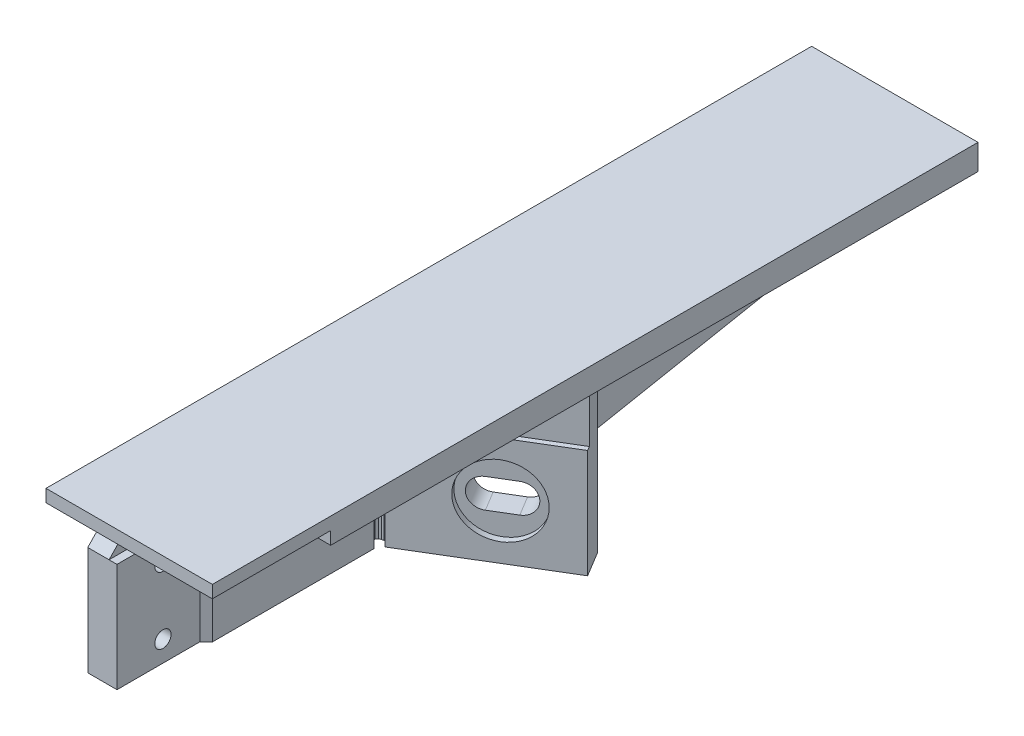
SolidWorks part; units mm, degrees
ref_plane "Front Plane" through (0, 0, 0) normal (0, 0, 1) x (1, 0, 0)
ref_plane "Top Plane" through (0, 0, 0) normal (0, 1, 0) x (1, 0, 0)
ref_plane "Right Plane" through (0, 0, 0) normal (1, 0, 0) x (0, 0, -1)
ref_plane "PY -20.700" through (0, -20.7, 0) normal (0, 1, 0) x (1, 0, 0)
sketch "leg and pad sketch" plane through (0, -20.7, 0) normal (0, 1, 0) x (1, 0, 0)
  line L0 (0.5513, 30.3327) -> (0.3673, 30.8194)
  line L1 (0.3673, 30.8194) -> (0.028, 31.2139)
  line L2 (0.028, 31.2139) -> (-0.4256, 31.4688)
  line L3 (-0.4256, 31.4688) -> (-0.939, 31.5534)
  line L4 (-0.939, 31.5534) -> (-1.4504, 31.4576)
  line L5 (-1.4504, 31.4576) -> (-1.8983, 31.1928)
  line L6 (-1.8983, 31.1928) -> (-2.2288, 30.7909)
  line L7 (-2.2288, 30.7909) -> (-2.4021, 30.3003)
  line L8 (-2.4021, 30.3003) -> (-2.3973, 29.78)
  line L9 (-2.3973, 29.78) -> (-2.2152, 29.2926)
  line L10 (-2.2152, 29.2926) -> (-1.8775, 28.8968)
  line L11 (-1.8775, 28.8968) -> (-1.4248, 28.6402)
  line L12 (-1.4248, 28.6402) -> (-0.9118, 28.5536)
  line L13 (-0.9118, 28.5536) -> (-0.4, 28.6475)
  line L14 (-0.4, 28.6475) -> (-0.4, -9.98)
  line L15 (-0.4, -9.98) -> (-1.92, -11.5)
  line L16 (-1.92, -11.5) -> (-1.92, -31.37)
  line L17 (-1.92, -31.37) -> (-8.92, -31.37)
  line L18 (-8.92, -31.37) -> (-8.92, 32.7926)
  line L19 (-8.92, 32.7926) -> (27.2048, 54.5947)
  line L20 (27.2048, 54.5947) -> (30.8218, 48.6015)
  line L21 (30.8218, 48.6015) -> (0.5513, 30.3327)
extrude "leg and pad" add sketch "leg and pad sketch" along normal mid plane 26
ref_plane "PX -1.350" through (-1.35, 0, 0) normal (1, 0, 0) x (0, 0, -1)
sketch "screw head relief sketch" plane through (-1.35, 0, 0) normal (1, 0, 0) x (0, 0, -1)
  line L0 (23.4, -12.7) -> (23.4, -6.7)
  line L1 (23.4, -6.7) -> (9.4, -6.7)
  line L2 (9.4, -6.7) -> (9.4, -12.7)
  line L3 (9.4, -12.7) -> (23.4, -12.7)
extrude "screw head relief" cut sketch "screw head relief sketch" against normal mid plane 4.7
sketch "insert flange relief sketch" plane through (0, -20.7, 0) normal (0, 1, 0) x (1, 0, 0)
  line L0 (18.3249, 39.8914) -> (17.0331, 42.0318)
  line L1 (17.0331, 42.0318) -> (9.7557, 37.6398)
  line L2 (9.7557, 37.6398) -> (11.0475, 35.4994)
  line L3 (11.0475, 35.4994) -> (18.3249, 39.8914)
revolve "insert flange relief" cut sketch "insert flange relief sketch" angle 360 about L0
sketch "M6 slot end 1 sketch" plane through (0, -20.7, 0) normal (0, 1, 0) x (1, 0, 0)
  line L0 (20.8933, 41.4415) -> (16.243, 49.147)
  line L1 (16.243, 49.147) -> (13.2464, 47.3385)
  line L2 (13.2464, 47.3385) -> (17.8968, 39.633)
  line L3 (17.8968, 39.633) -> (20.8933, 41.4415)
revolve "M6 slot end 1" cut sketch "M6 slot end 1 sketch" angle 360 about L0
sketch "M6 slot end 2 sketch" plane through (0, -20.7, 0) normal (0, 1, 0) x (1, 0, 0)
  line L0 (15.7564, 38.3413) -> (11.106, 46.0467)
  line L1 (11.106, 46.0467) -> (8.1094, 44.2382)
  line L2 (8.1094, 44.2382) -> (12.7598, 36.5328)
  line L3 (12.7598, 36.5328) -> (15.7564, 38.3413)
revolve "M6 slot end 2" cut sketch "M6 slot end 2 sketch" angle 360 about L0
sketch "M6 slot middle sketch" plane through (0, -20.7, 0) normal (0, 1, 0) x (1, 0, 0)
  line L0 (15.7564, 38.3413) -> (20.8933, 41.4415)
  line L1 (20.8933, 41.4415) -> (16.243, 49.147)
  line L2 (16.243, 49.147) -> (11.106, 46.0467)
  line L3 (11.106, 46.0467) -> (15.7564, 38.3413)
extrude "M6 slot middle" cut sketch "M6 slot middle sketch" against normal mid plane 7
ref_plane "PX -5.420" through (-5.42, 0, 0) normal (1, 0, 0) x (0, 0, -1)
sketch "screw holes sketch" plane through (-5.42, 0, 0) normal (1, 0, 0) x (0, 0, -1)
  circle A0 centre (-20.375, -28.7) radius 1.95
  circle A1 centre (-20.375, -12.7) radius 1.95
extrude "screw holes" cut sketch "screw holes sketch" against normal mid plane 9
ref_plane "PY -2.100" through (0, -2.1, 0) normal (0, 1, 0) x (1, 0, 0)
sketch "foot leg sketch" plane through (0, -2.1, 0) normal (0, 1, 0) x (1, 0, 0)
  line L0 (-2.3, 30.0135) -> (-2.3, -9.98)
  line L1 (-2.3, -9.98) -> (-8.92, -9.98)
  line L2 (-8.92, -9.98) -> (-8.92, 32.7926)
  line L3 (-8.92, 32.7926) -> (27.2048, 54.5947)
  line L4 (27.2048, 54.5947) -> (30.2017, 49.6289)
  line L5 (30.2017, 49.6289) -> (-2.3, 30.0135)
extrude "foot leg" add sketch "foot leg sketch" along normal mid plane 12.2
ref_plane "PY 6.535" through (0, 6.535, 0) normal (0, 1, 0) x (1, 0, 0)
sketch "sole under the housing sketch" plane through (0, 6.535, 0) normal (0, 1, 0) x (1, 0, 0)
  line L0 (30.9218, 142) -> (-8.92, 142)
  line L1 (-8.92, 142) -> (-8.92, -13.03)
  line L2 (-8.92, -13.03) -> (30.9218, -13.03)
  line L3 (30.9218, -13.03) -> (30.9218, 142)
extrude "sole under the housing" add sketch "sole under the housing sketch" along normal mid plane 6.07
ref_plane "PY 8.070" through (0, 8.07, 0) normal (0, 1, 0) x (1, 0, 0)
sketch "sole under the block sketch" plane through (0, 8.07, 0) normal (0, 1, 0) x (1, 0, 0)
  line L0 (30.9218, -12.53) -> (-8.92, -12.53)
  line L1 (-8.92, -12.53) -> (-8.92, -41.37)
  line L2 (-8.92, -41.37) -> (30.9218, -41.37)
  line L3 (30.9218, -41.37) -> (30.9218, -12.53)
extrude "sole under the block" add sketch "sole under the block sketch" along normal mid plane 3
ref_plane "PX -6.370" through (-6.37, 0, 0) normal (1, 0, 0) x (0, 0, -1)
sketch "seat gusset sketch" plane through (-6.37, 0, 0) normal (1, 0, 0) x (0, 0, -1)
  line L0 (-9.48, -8.2) -> (-31.37, -8.2)
  line L1 (-31.37, -8.2) -> (-31.37, -7.7)
  line L2 (-31.37, -7.7) -> (-17.1, 7.07)
  line L3 (-17.1, 7.07) -> (-9.48, 7.07)
  line L4 (-9.48, 7.07) -> (-9.48, -8.2)
extrude "seat gusset" add sketch "seat gusset sketch" along normal mid plane 5.1
ref_plane "PX 19.922" through (19.9218, 0, 0) normal (1, 0, 0) x (0, 0, -1)
sketch "tail rib sketch" plane through (19.9218, 0, 0) normal (1, 0, 0) x (0, 0, -1)
  line L0 (53.1, 4) -> (53.1, -12.5)
  line L1 (53.1, -12.5) -> (57.1, -12.5)
  line L2 (57.1, -12.5) -> (140, 3.5)
  line L3 (140, 3.5) -> (140, 4)
  line L4 (140, 4) -> (53.1, 4)
extrude "tail rib" add sketch "tail rib sketch" along normal mid plane 6
sketch "screw head relief to the end sketch" plane through (-1.35, 0, 0) normal (1, 0, 0) x (0, 0, -1)
  line L0 (23.4, -12.7) -> (23.4, 3.3)
  line L1 (23.4, 3.3) -> (9.4, 3.3)
  line L2 (9.4, 3.3) -> (9.4, -12.7)
  line L3 (9.4, -12.7) -> (23.4, -12.7)
extrude "screw head relief to the end" cut sketch "screw head relief to the end sketch" against normal mid plane 4.7
equation "\"diffL\" = 608.8mm"
equation "\"diffW\" = 329.4mm"
equation "\"diffT\" = 2.9mm"
equation "\"chanSlotW\" = 12.9mm"
equation "\"chanSlotDepth\" = 11.13mm"
equation "\"chanFloor\" = 1.57mm"
equation "\"chanLeg\" = 12.7mm"
equation "\"lightL\" = 604.8mm"
equation "\"lightW\" = 330.2mm"
equation "\"lightH\" = 92mm"
equation "\"lightSideFlat\" = 30mm"
equation "\"lightSlopeLen\" = 38.9mm"
equation "\"lightWingDepth\" = 50.1mm"
equation "\"lightWingFlat\" = 90.2mm"
equation "\"lightChanW\" = 99.6mm"
equation "\"lightChanStand\" = 44.1mm"
equation "\"insFlangeD\" = 12.3mm"
equation "\"insFromEnd\" = 20.7mm"
equation "\"insUpSlope\" = 20.8mm"
equation "\"gaugeH\" = 10mm"
equation "\"gaugeStepLen\" = 14mm"
equation "\"gaugeStepW0\" = 13.1mm"
equation "\"gaugeStepDW\" = 0.2mm"
equation "\"gaugeSteps\" = 5mm"
equation "\"gaugeHandleLen\" = 30mm"
equation "\"gaugeHandleW\" = 24mm"
equation "\"gaugeSlot0\" = 3mm"
equation "\"gaugeSlotD\" = 0.1mm"
equation "\"gaugeSlotDepth\" = 8mm"
equation "\"gap\" = 25.4mm"
equation "\"edgeL\" = 1mm"
equation "\"edgeW\" = 0.75mm"
equation "\"proud\" = 1.5mm"
equation "\"seatClr\" = 0.15mm"
equation "\"tongueClrZ\" = 0.1mm"
equation "\"tongueClrX\" = 0.25mm"
equation "\"tongueLen\" = 30mm"
equation "\"armSide\" = 45mm"
equation "\"armEnd\" = 20mm"
equation "\"cornerCham\" = 3mm"
equation "\"brkW\" = 26mm"
equation "\"brkT\" = 7mm"
equation "\"brkSeatClr\" = 0.3mm"
equation "\"brkScrewSpan\" = 16mm"
equation "\"pilotD\" = 2.7mm"
equation "\"pilotDepth\" = 10mm"
equation "\"screwClrD\" = 3.9mm"
equation "\"jogBelow\" = 4mm"
equation "\"padT\" = 7mm"
equation "\"padLen\" = 36mm"
equation "\"m6Clr\" = 7mm"
equation "\"m6Slot\" = 6mm"
equation "\"flangeRelD\" = 17mm"
equation "\"flangeRelDepth\" = 1.5mm"
equation "\"relLen\" = 5mm"
equation "\"relDepth\" = 3.3mm"
equation "\"knockN\" = 100mm"
equation "\"petgcfE\" = 3000mm"
equation "\"mockExtent\" = 110mm"
equation "\"relZnear\" = 9.4mm"
equation "\"relZfar\" = 23.4mm"
equation "\"headD\" = 8mm"
equation "\"headH\" = 2.5mm"
equation "\"headFromEnd\" = 6.8mm"
equation "\"headBack\" = 16.4mm"
equation "\"sideClr\" = 0.4mm"
equation "\"cornerRelR\" = 1.5mm"
equation "\"cornerRelBack\" = 0.6mm"
equation "\"endHeadH\" = 2.8mm"
equation "\"footClr\" = 1.2mm"
equation "\"footEndClr\" = 3.5mm"
equation "\"footLift\" = 3.5mm"
equation "\"footBlockClr\" = 0.5mm"
equation "\"footBack\" = 30mm"
equation "\"footFwd\" = 25mm"
equation "\"footRibH\" = 16mm"
equation "\"footRibT\" = 6mm"
